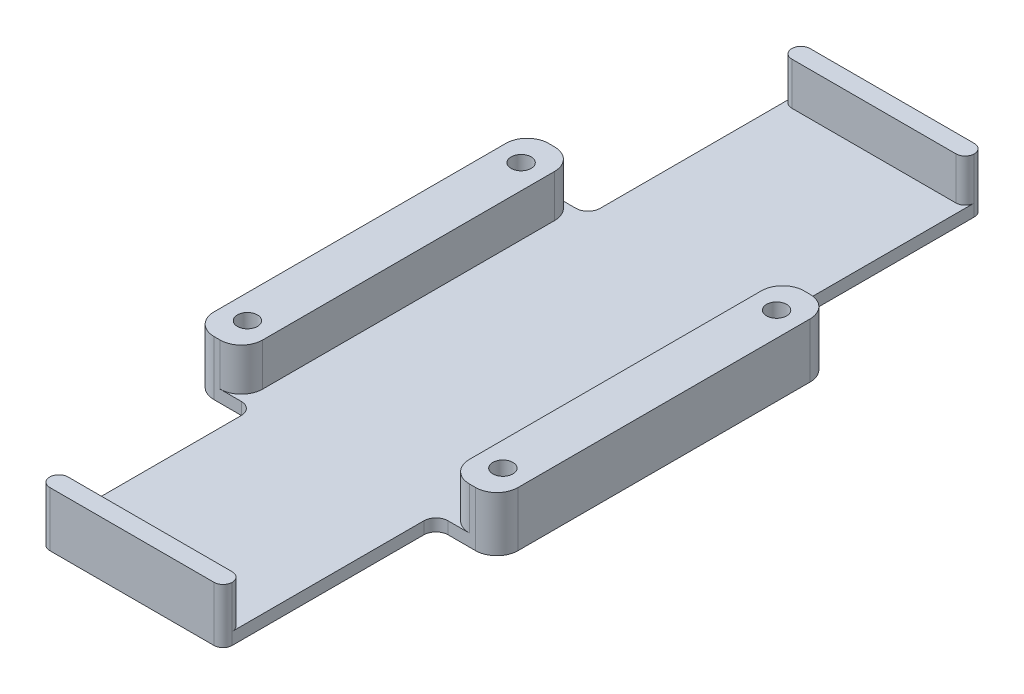
SolidWorks part; units mm, degrees
ref_plane "Спереди" through (0, 0, 0) normal (0, 0, 1) x (1, 0, 0)
ref_plane "Сверху" through (0, 0, 0) normal (0, 1, 0) x (1, 0, 0)
ref_plane "Справа" through (0, 0, 0) normal (1, 0, 0) x (0, 0, -1)
sketch "Эскиз1" plane through (0, 0, 0) normal (0, 1, 0) x (1, 0, 0)
  line L0 (0, 62.5) -> (0, -62.5) construction
  line L1 (-25, 62.5) -> (25, 62.5)
  line L2 (-25, 62.5) -> (-25, -62.5)
  line L3 (-25, -62.5) -> (25, -62.5)
  line L4 (25, 62.5) -> (25, -62.5)
  line L6 (-25, 0) -> (25, 0) construction
  point P6 (0, 0)
  dimension "D1" = 125
  dimension "D2" = 50
extrude "тело" add sketch "Эскиз1" along normal blind 2
sketch "Эскиз2" plane through (0, 2, 0) normal (0, 1, 0) x (1, 0, 0)
  line L0 (0, 62.5) -> (0, -62.5) construction
  line L1 (25, 62.5) -> (-25, 62.5) construction
  line L2 (-25, -62.5) -> (25, -62.5) construction
  line L4 (-25, 62.5) -> (-25, -62.5) construction
  line L5 (-25, 0) -> (25, 0) construction
  line L6 (25, -62.5) -> (25, 62.5) construction
  line L7 (-25, 62.5) -> (-15, 62.5)
  line L8 (-25, 62.5) -> (-25, 27.5)
  line L9 (-25, 27.5) -> (-15, 27.5)
  line L10 (-15, 62.5) -> (-15, 27.5)
  line L11 (25, 62.5) -> (15, 62.5)
  line L12 (25, 62.5) -> (25, 27.5)
  line L13 (25, 27.5) -> (15, 27.5)
  line L14 (15, 62.5) -> (15, 27.5)
  line L15 (25, -62.5) -> (15, -62.5)
  line L16 (25, -62.5) -> (25, -27.5)
  line L17 (25, -27.5) -> (15, -27.5)
  line L18 (15, -62.5) -> (15, -27.5)
  line L19 (-25, -62.5) -> (-15, -62.5)
  line L20 (-25, -62.5) -> (-25, -27.5)
  line L21 (-25, -27.5) -> (-15, -27.5)
  line L22 (-15, -62.5) -> (-15, -27.5)
  dimension "D1" = 55
  dimension "D2" = 30
extrude "пазы чтоб добраться до винтов" cut sketch "Эскиз2" against normal through all
sketch "Эскиз3" plane through (0, 2, 0) normal (0, 1, 0) x (1, 0, 0)
  line L0 (-25, 0) -> (25, 0) construction
  line L1 (-25, 27.5) -> (-25, -27.5) construction
  line L2 (25, -27.5) -> (25, 27.5) construction
  line L3 (0, 62.5) -> (0, -62.5) construction
  line L4 (15, 62.5) -> (-15, 62.5) construction
  line L5 (-15, -62.5) -> (15, -62.5) construction
  line L7 (-25, 27.5) -> (-17, 27.5)
  line L8 (-25, 27.5) -> (-25, -27.5)
  line L9 (-25, -27.5) -> (-17, -27.5)
  line L10 (-17, 27.5) -> (-17, -27.5)
  line L11 (25, 27.5) -> (17, 27.5)
  line L12 (25, 27.5) -> (25, -27.5)
  line L13 (25, -27.5) -> (17, -27.5)
  line L14 (17, 27.5) -> (17, -27.5)
  point P20 (17, 0)
  point P21 (-17, 0)
  dimension "D1" = 34
  dimension "D2" = 55
extrude "крепление к аккумулятору" add sketch "Эскиз3" along normal blind 7
sketch "Эскиз4" plane through (0, 2, 0) normal (0, 1, 0) x (1, 0, 0)
  line L0 (0, 62.5) -> (0, -62.5) construction
  line L1 (15, 62.5) -> (-15, 62.5) construction
  line L2 (-15, -62.5) -> (15, -62.5) construction
  line L4 (-15, 62.5) -> (15, 62.5)
  line L5 (-15, 62.5) -> (-15, 59.5)
  line L6 (-15, 59.5) -> (15, 59.5)
  line L7 (15, 62.5) -> (15, 59.5)
  line L8 (-15, -62.5) -> (15, -62.5)
  line L9 (-15, -62.5) -> (-15, -59.5)
  line L10 (-15, -59.5) -> (15, -59.5)
  line L11 (15, -62.5) -> (15, -59.5)
  point P14 (0, -59.5)
  point P15 (0, 59.5)
  dimension "D1" = 30
  dimension "D2" = 119
extrude "выступы фиксации аккума" add sketch "Эскиз4" along normal blind 7
sketch "Эскиз5" plane through (0, 9, 0) normal (0, 1, 0) x (1, 0, 0)
  line L0 (-25, 0) -> (25, 0) construction
  line L1 (-25, 27.5) -> (-25, -27.5) construction
  line L2 (25, -27.5) -> (25, 27.5) construction
  line L3 (-21, 27.5) -> (-21, -27.5) construction
  line L4 (15, 62.5) -> (-15, 62.5) construction
  line L5 (0, 62.5) -> (0, -62.5) construction
  line L6 (-15, -62.5) -> (15, -62.5) construction
  line L7 (-17, 27.5) -> (-25, 27.5) construction
  line L8 (-25, -27.5) -> (-17, -27.5) construction
  line L10 (25, 27.5) -> (17, 27.5) construction
  line L11 (21, 27.5) -> (21, -27.5) construction
  line L12 (17, -27.5) -> (25, -27.5) construction
  circle A0 centre (-21, 22.5) radius 1.65
  circle A1 centre (-21, -22.5) radius 1.65
  circle A2 centre (21, -22.5) radius 1.65
  circle A3 centre (21, 22.5) radius 1.65
  dimension "D1" = 3.3
  dimension "D2" = 45
extrude "отверстия для шурупов" cut sketch "Эскиз5" against normal through all
sketch "Эскиз7" plane through (0, 0, 0) normal (0, -1, 0) x (1, 0, 0)
  circle A0 centre (-21, 22.5) radius 3.2
  circle A1 centre (-21, -22.5) radius 3.2
  circle A2 centre (21, 22.5) radius 3.2
  circle A3 centre (21, -22.5) radius 3.2
  dimension "D1" = 6.4
extrude "углубления для шляпок" cut sketch "Эскиз7" against normal blind 4
chamfer "Фаска1" [suppressed] distance 1.5 angle 45
fillet "Скругление1" radius 1.5 8 edges at (-15, 5.5, 59.5) (-15, 4.5, 62.5) (15, 4.5, 62.5) (15, 5.5, 59.5) (15, 4.5, -62.5) (15, 5.5, -59.5) (-15, 5.5, -59.5) (-15, 4.5, -62.5)
fillet "Скругление2" radius 2 4 edges at (15, 1, -27.5) (-15, 1, -27.5) (-15, 1, 27.5) (15, 1, 27.5)
fillet "Скругление3" radius 3.5 8 edges at (-17, 5.5, 27.5) (-25, 4.5, 27.5) (-25, 4.5, -27.5) (-17, 5.5, -27.5) (25, 4.5, -27.5) (17, 5.5, -27.5) (17, 5.5, 27.5) (25, 4.5, 27.5)
